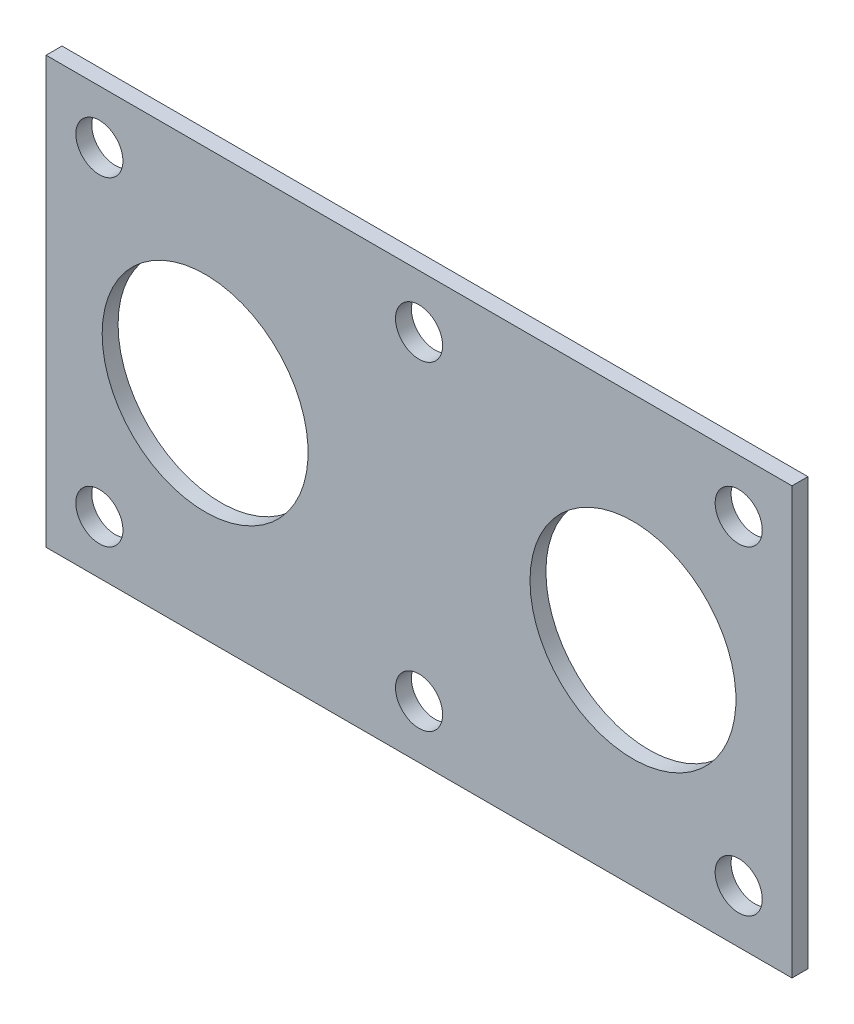
SolidWorks part; units mm, degrees
material "Plain Carbon Steel"
ref_plane "Front Plane" through (0, 0, 0) normal (0, 0, 1) x (1, 0, 0)
ref_plane "Top Plane" through (0, 0, 0) normal (0, 1, 0) x (1, 0, 0)
ref_plane "Right Plane" through (0, 0, 0) normal (1, 0, 0) x (0, 0, -1)
sketch "Sketch1" plane through (0, 0, 0) normal (0, 0, 1) x (1, 0, 0)
  line L1 (-18.9548, 25.4) -> (69.9452, 25.4)
  line L2 (-18.9548, 25.4) -> (-18.9548, -25.4)
  line L3 (-18.9548, -25.4) -> (69.9452, -25.4)
  line L4 (69.9452, 25.4) -> (69.9452, -25.4)
  circle A0 centre (0, 0) radius 12.2726
  circle A1 centre (50.9905, 0) radius 12.2726
  circle A2 centre (50.9905, 0) radius 12.2726 construction
  circle A3 centre (0, 0) radius 12.2726 construction
extrude "Boss-Extrude1" add sketch "Sketch1" along normal blind 1.8974
hole_wizard "#10 Clearance Hole1" positions "Sketch3" profile "Sketch4" hole size "#10" standard "ANSI Inch" end condition through all
sketch "Sketch3" plane through (-41.275, -44.45, 1.8974) normal (0, 0, 1) x (1, 0, 0)
  line L16 (28.6702, 63.5) -> (28.6702, 25.4)
  line L17 (28.6702, 25.4) -> (104.8702, 25.4)
  line L18 (104.8702, 25.4) -> (104.8702, 63.5)
  line L19 (104.8702, 63.5) -> (28.6702, 63.5)
  point P0 (104.8702, 63.5)
  point P2 (28.6702, 63.5)
  point P4 (66.7702, 25.4)
  point P6 (28.6702, 25.4)
  point P8 (66.7702, 63.5)
  point P10 (104.8702, 25.4)
  point P22 (0, 0)
  point P51 (24.8602, 67.31)
  point P52 (66.7702, 67.31)
  point P53 (108.6802, 67.31)
  point P54 (108.6802, 21.59)
  point P55 (66.7702, 21.59)
  point P56 (24.8602, 21.59)
sketch "Sketch4" plane through (63.5952, 19.05, 1.8974) normal (1, 0, 0) x (0, -1, 0)
  line L0 (0, 0) -> (0, 1.8974)
  line L1 (0, 1.8974) -> (2.8067, 1.8974)
  line L2 (2.8067, 1.8974) -> (2.8067, 0)
  line L5 (2.8067, 0) -> (0, 0)
  line L11 (0, -6.35) -> (0, 107.95) construction
  dimension "Thru Hole Dia." = 5.6134
  dimension "Thru Hole Depth" = 1.8974
